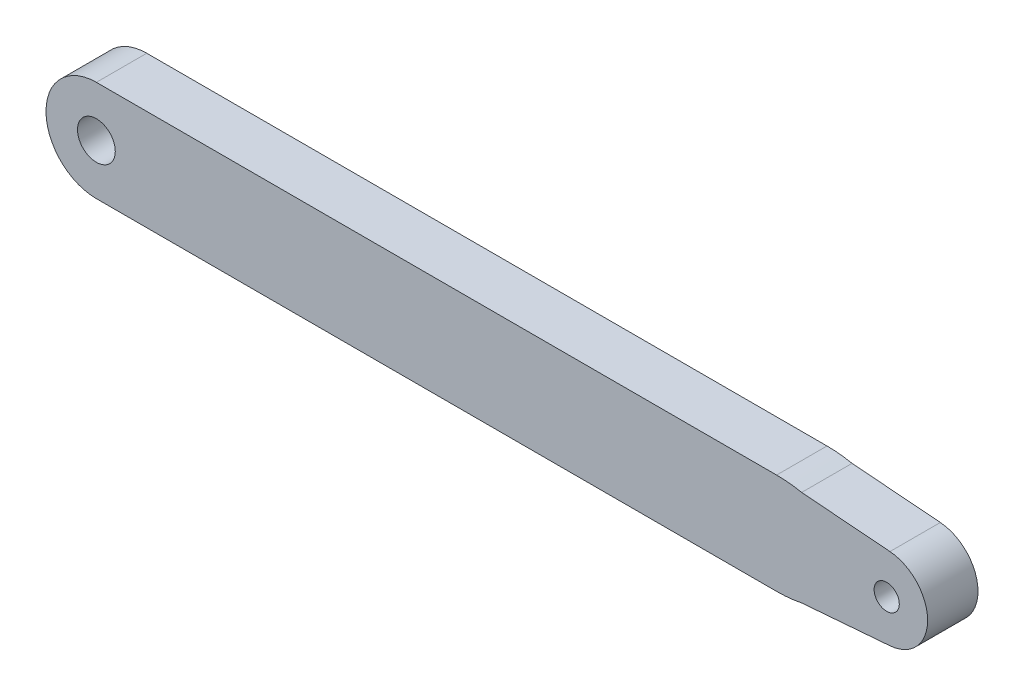
SolidWorks part; units mm, degrees
ref_plane "Front Plane" through (0, 0, 0) normal (0, 0, 1) x (1, 0, 0)
ref_plane "Top Plane" through (0, 0, 0) normal (0, 1, 0) x (1, 0, 0)
ref_plane "Right Plane" through (0, 0, 0) normal (1, 0, 0) x (0, 0, -1)
sketch "Sketch1" plane through (0, 0, 0) normal (0, 0, 1) x (1, 0, 0)
  line L1 (-175, 20) -> (175, 20)
  line L2 (-175, 20) -> (-175, -20)
  line L3 (-175, -20) -> (175, -20)
  line L4 (175, 20) -> (175, -20)
  line L5 (-175, 20) -> (175, -20) construction
  line L6 (-175, -20) -> (175, 20) construction
  point P0 (0, 0)
  dimension "D1" = 350
  dimension "D2" = 40
extrude "Boss-Extrude1" add sketch "Sketch1" along normal blind 20
sketch "Sketch2" plane through (0, 0, 20) normal (0, 0, 1) x (1, 0, 0)
  line L0 (175, 20) -> (175, 15)
  line L1 (175, -20) -> (175, 20) construction
  line L2 (175, 15) -> (125, 19)
  line L3 (125, 19) -> (125, 20)
  line L4 (175, 20) -> (-175, 20) construction
  line L5 (125, 20) -> (175, 20)
  dimension "D1" = 50
  dimension "D2" = 1
  dimension "D3" = 5
extrude "Cut-Extrude1" cut sketch "Sketch2" against normal through all
fillet "Fillet1" radius 50 1 edges at (125, 20, 10)
mirror "Mirror3" about plane through (0, 0, 0) normal (0, 1, 0) of "Cut-Extrude1"
fillet "Fillet2" radius 50 1 edges at (125, -20, 10)
fillet "Fillet3" 2 edges at (175, 15, 10) (175, -15, 10) type full round first side face at (150, 17, 10) second side face at (150, -17, 10) middle face at (175, 0, 10)
fillet "Fillet4" 2 edges at (-175, 20, 10) (-175, -20, 10) type full round first side face at (-29.9749, 20, 10) second side face at (-29.9749, -20, 10) middle face at (-175, 0, 10)
sketch "Sketch3" plane through (0, 0, 20) normal (0, 0, 1) x (1, 0, 0)
  circle A0 centre (-155, 0) radius 7.5
  circle A1 centre (158.7521, 0) radius 5
  dimension "D1" = 15
  dimension "D2" = 10
extrude "Cut-Extrude2" cut sketch "Sketch3" against normal through all
